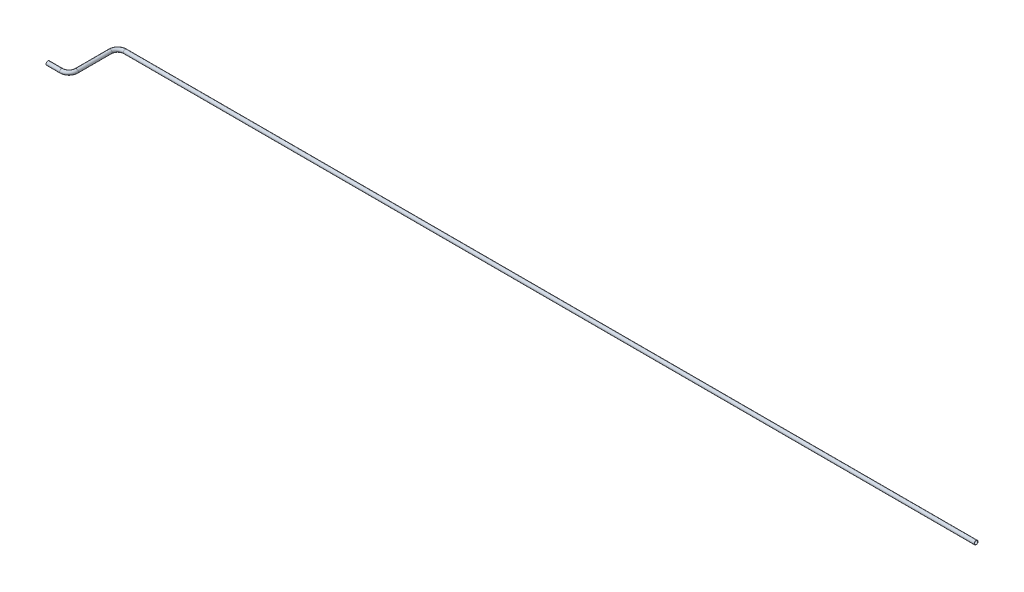
SolidWorks part; units mm, degrees
material "AISI Type 316L stainless steel"
ref_plane "Front Plane" through (0, 0, 0) normal (0, 0, 1) x (1, 0, 0)
ref_plane "Top Plane" through (0, 0, 0) normal (0, 1, 0) x (1, 0, 0)
ref_plane "Right Plane" through (0, 0, 0) normal (1, 0, 0) x (0, 0, -1)
sketch3d "3DSketch1"
  line L1 (0, 0, 0) -> (22.86, 0, 0)
  line L2 (35.56, 0, -12.7) -> (35.56, 0, -69.4883)
  line L3 (48.26, 0, -82.1883) -> (1483.36, 0, -82.1883)
  arc A1 (35.56, 0, -69.4883) -> (48.26, 0, -82.1883) centre (48.26, 0, -69.4883) ccw
  arc A2 (22.86, 0, 0) -> (35.56, 0, -12.7) centre (22.86, 0, -12.7) ccw
  point P2 (0, 0, 0)
  point P16 (35.56, 0, -82.1883)
  point P17 (48.26, -12.7, -69.4883)
  point P20 (35.56, 0, 0)
  point P22 (22.86, 12.7, -12.7)
  dimension "D7" = 12.7
  dimension "D1" = 35.56
  dimension "D2" = 82.1883
  dimension "D3" = 1447.8
ref_plane "Plane4" through (0, 0, 0) normal (1, 0, 0) x (0, 0, -1)
sketch "Sketch5" plane through (0, 0, 0) normal (1, 0, 0) x (0, 0, -1)
  circle A0 centre (0, 0) radius 3.175
  circle A1 centre (0, 0) radius 2.667
  dimension "D1" = 6.35
  dimension "D2" = 0.508
sweep "Sweep3" add profiles "Sketch5" path "3DSketch1"
